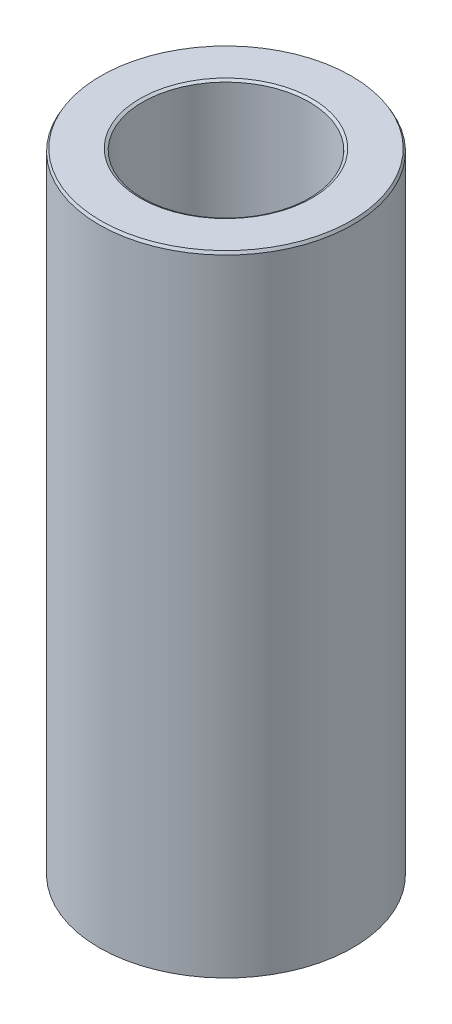
SolidWorks part; units mm, degrees
ref_plane "Front Plane" through (0, 0, 0) normal (0, 0, 1) x (1, 0, 0)
ref_plane "Top Plane" through (0, 0, 0) normal (0, 1, 0) x (1, 0, 0)
ref_plane "Right Plane" through (0, 0, 0) normal (1, 0, 0) x (0, 0, -1)
sketch "Sketch1" plane through (0, 0, 0) normal (0, 1, 0) x (1, 0, 0)
  circle A0 centre (0, 0) radius 15
  dimension "SLEEVE_OD" = 30
extrude "Boss-Extrude1" add sketch "Sketch1" along normal blind 74.5081
sketch "Sketch2" plane through (0, 0, 0) normal (0, 1, 0) x (1, 0, 0)
  circle A0 centre (0, 0) radius 9.8523
  dimension "BORE_D" = 19.7046
extrude "Cut-Extrude1" cut sketch "Sketch2" along normal through all
chamfer "Chamfer1" distance 0.324 angle 30 4 edges at (0, 74.5081, 9.8523) (0, 0, 9.8523) (0, 0, 15) (0, 74.5081, 15) first distance on face at (0, 74.5081, 9.8523) first distance on face at (0, 0, 9.8523) first distance on face at (0, 74.5081, 15)
